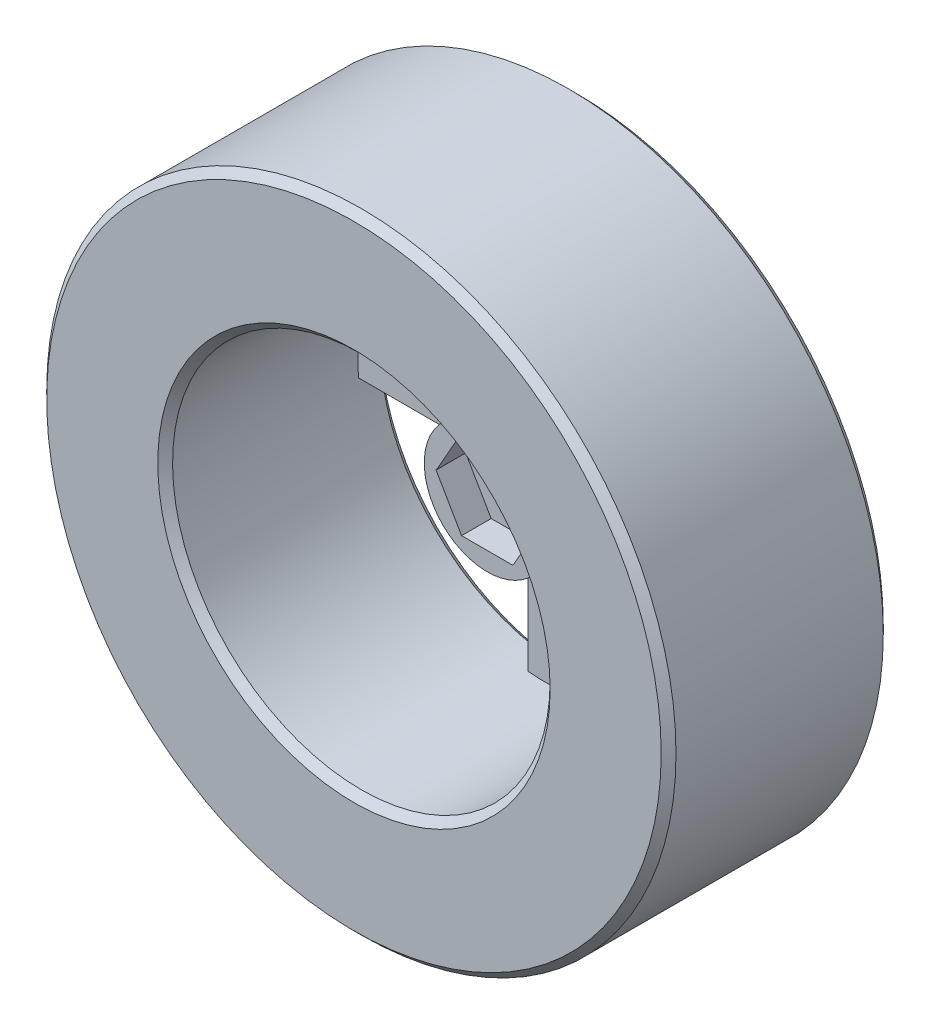
SolidWorks part; units mm, degrees
ref_plane "前视基准面" through (0, 0, 0) normal (0, 0, 1) x (1, 0, 0)
ref_plane "上视基准面" through (0, 0, 0) normal (0, 1, 0) x (1, 0, 0)
ref_plane "右视基准面" through (0, 0, 0) normal (1, 0, 0) x (0, 0, -1)
sketch "草图1" plane through (0, 0, 0) normal (0, 0, 1) x (1, 0, 0)
  line L0 (2.5, -8.124) -> (2.5, -25.3772)
  line L1 (25.3772, -2.5) -> (8.124, -2.5)
  line L2 (-25.3772, 2.5) -> (-8.124, 2.5)
  line L3 (-2.5, -8.124) -> (-2.5, -25.3772)
  line L4 (2.5, 25.3772) -> (2.5, 8.124)
  line L5 (-2.5, 25.3772) -> (-2.5, 8.124)
  line L6 (8.124, 2.5) -> (25.3772, 2.5)
  line L7 (-8.124, -2.5) -> (-25.3772, -2.5)
  circle A0 centre (0, 0) radius 8.5
  circle A1 centre (0, 0) radius 25.5
  circle A2 centre (0, 0) radius 85
extrude "凸台-拉伸3" add sketch "草图1" along normal blind 4 contours L4 A1 L5 A0 | L1 A1 L6 A0 | L3 A1 L0 A0 | L2 A1 L7 A0 region at (0, -16.9171, 0) region at (16.9171, 0, 0) region at (-16.9171, 0, 0) region at (0, 16.9171, 0)
sketch "草图2" plane through (0, 0, 0) normal (0, 0, 1) x (1, 0, 0)
  circle A0 centre (0, 0) radius 25.5
  circle A1 centre (0, 0) radius 85
extrude "凸台-拉伸4" add sketch "草图2" along normal blind 30
sketch "草图3" plane through (0, 0, 0) normal (0, 0, 1) x (1, 0, 0)
  circle A0 centre (0, 0) radius 8.5
extrude "凸台-拉伸5" add sketch "草图3" along normal blind 12
sketch "草图4" plane through (0, 0, 12) normal (0, 0, 1) x (1, 0, 0)
  line L5 (-3.465, 6.0016) -> (3.465, 6.0016)
  line L6 (3.465, 6.0016) -> (6.93, 0)
  line L7 (6.93, 0) -> (3.465, -6.0016)
  line L8 (3.465, -6.0016) -> (-3.465, -6.0016)
  line L9 (-3.465, -6.0016) -> (-6.93, 0)
  line L10 (-6.93, 0) -> (-6.8414, 0.0221)
  line L11 (-6.8414, 0.0221) -> (-3.465, 6.0016)
extrude "切除-拉伸1" cut sketch "草图4" against normal blind 4
chamfer "倒角1" distance 1 angle 45 1 edges at (85, 0, 0)
chamfer "倒角2" distance 1 angle 45 1 edges at (85, 0, 30)
chamfer "倒角3" distance 1 angle 45 1 edges at (25.5, 0, 30)
chamfer "倒角4" distance 1 angle 45 4 edges at (18.0312, -18.0312, 0) (-18.0312, -18.0312, 0) (18.0312, 18.0312, 0) (-18.0312, 18.0312, 0)
sketch "草图5" plane through (0, 0, 0) normal (0, 0, 1) x (1, 0, 0)
  circle A0 centre (0, 0) radius 42.5
  circle A1 centre (0, 0) radius 115.0631
extrude "切除-拉伸2" cut sketch "草图5" along normal blind 40
chamfer "倒角5" distance 1 angle 45 2 edges at (42.5, 0, 30) (42.5, 0, 0)
